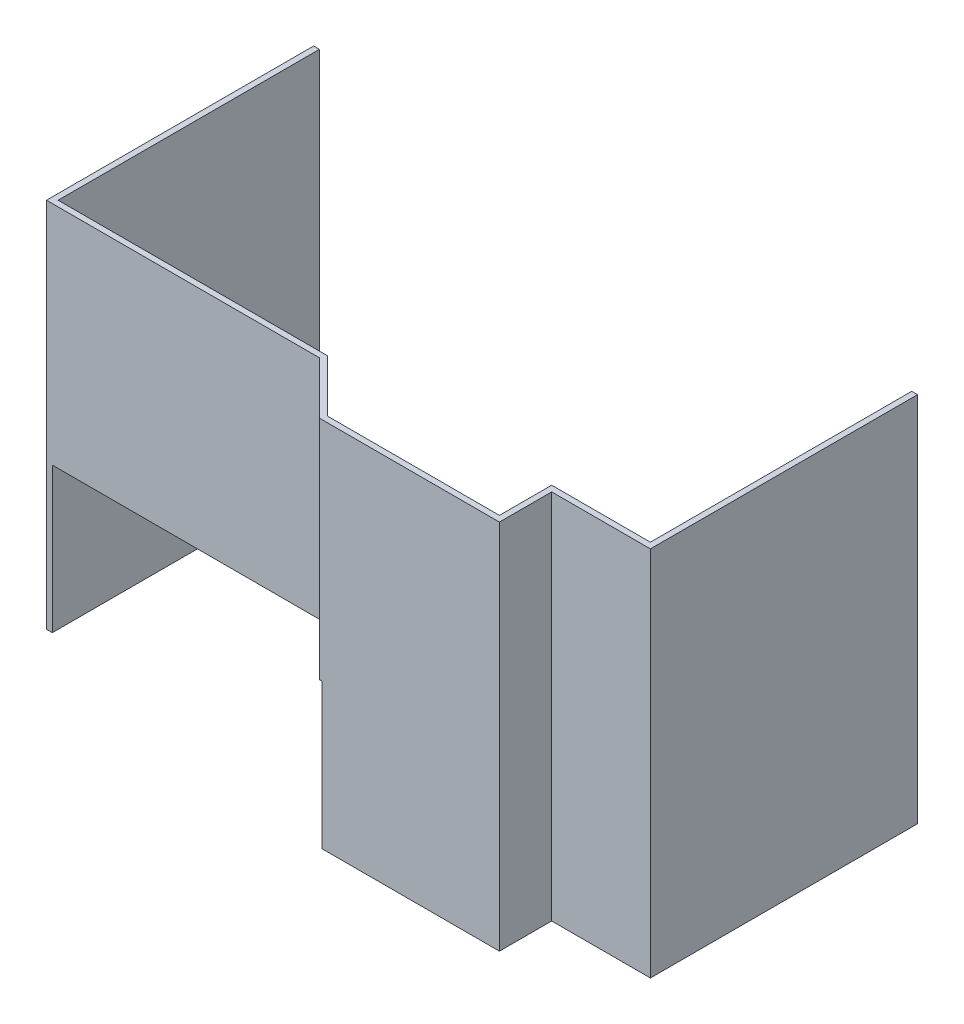
SolidWorks part; units mm, degrees
ref_plane "Front Plane" through (0, 0, 0) normal (0, 0, 1) x (1, 0, 0)
ref_plane "Top Plane" through (0, 0, 0) normal (0, 1, 0) x (1, 0, 0)
ref_plane "Right Plane" through (0, 0, 0) normal (1, 0, 0) x (0, 0, -1)
sketch "Sketch1" plane through (0, 0, 0) normal (0, 1, 0) x (1, 0, 0)
  line L0 (0, 0) -> (0, 292.1)
  line L1 (0, 292.1) -> (6.35, 292.1)
  line L2 (6.35, 292.1) -> (6.35, 6.35)
  line L3 (6.35, 6.35) -> (301.0803, 6.35)
  line L4 (0, 0) -> (298.45, 0)
  line L5 (298.45, 0) -> (355.6, -57.15)
  line L6 (355.6, -57.15) -> (552.45, -57.15)
  line L8 (552.45, 0) -> (660.4, 0)
  line L9 (660.4, 0) -> (660.4, 292.1)
  line L10 (660.4, 292.1) -> (654.05, 292.1)
  line L11 (654.05, 292.1) -> (654.05, 6.35)
  line L12 (654.05, 6.35) -> (546.1, 6.35)
  line L14 (546.1, -50.8) -> (358.2303, -50.8)
  line L15 (358.2303, -50.8) -> (301.0803, 6.35)
  line L16 (546.1, 6.35) -> (546.1, -50.8)
  line L17 (552.45, -57.15) -> (552.45, 0)
  dimension "D1" = 292.1
  dimension "D2" = 6.35
  dimension "D3" = 6.35
  dimension "D4" = 6.35
  dimension "D5" = 6.35
  dimension "D6" = 6.35
  dimension "D7" = 6.35
  dimension "D8" = 6.35
  dimension "D9" = 660.4
  dimension "D10" = 254
  dimension "D11" = 107.95
  dimension "D12" = 135
  dimension "D13" = 57.15
  dimension "D14" = 6.35
extrude "Boss-Extrude1" add sketch "Sketch1" along normal blind 406.4
sketch "Sketch2" plane through (0, 0, 57.15) normal (0, 0, 1) x (1, 0, 0)
  line L0 (355.6, 0) -> (552.45, 0) construction
  line L1 (358.2303, 0) -> (88.9, 0)
  line L2 (358.2303, 0) -> (358.2303, 158.75)
  line L3 (358.2303, 158.75) -> (6.35, 158.75)
  line L5 (6.35, 406.4) -> (6.35, 0) construction
  line L6 (88.9, 0) -> (6.35, 0)
  line L11 (6.35, 0) -> (6.35, 158.75)
  line L13 (358.2303, 406.4) -> (358.2303, 0) construction
  point P9 (6.35, 158.75)
  point P10 (6.35, 155.7741)
  point P15 (358.2303, 158.75)
  dimension "D1" = 158.75
extrude "Cut-Extrude1" cut sketch "Sketch2" against normal up to surface (63.5 mm away) up to face at (153.7151, 203.2, -6.35)
